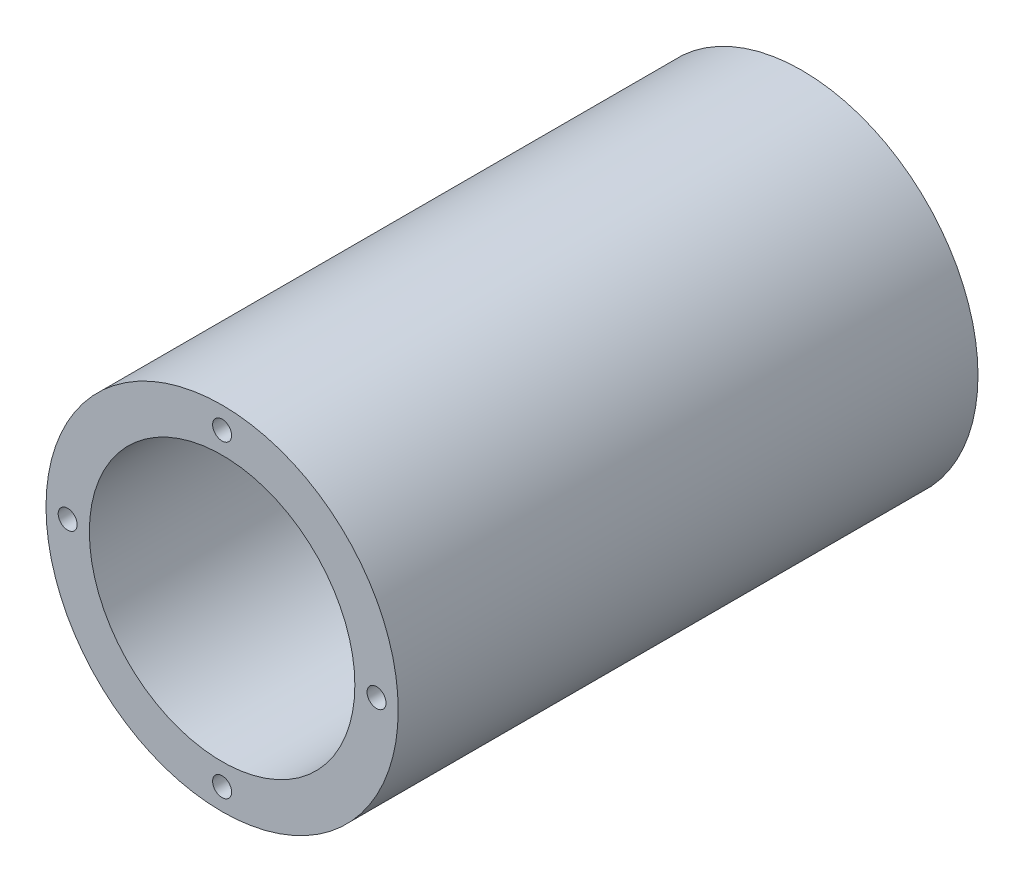
SolidWorks part; units mm, degrees
ref_plane "Alzado" through (0, 0, 0) normal (0, 0, 1) x (1, 0, 0)
ref_plane "Planta" through (0, 0, 0) normal (0, 1, 0) x (1, 0, 0)
ref_plane "Vista lateral" through (0, 0, 0) normal (1, 0, 0) x (0, 0, -1)
sketch "Croquis1" plane through (0, 0, 0) normal (0, 0, 1) x (1, 0, 0)
  circle A0 centre (0, 0) radius 32.5
  circle A1 centre (0, 0) radius 24.5
  dimension "D1" = 65
  dimension "D2" = 8
extrude "Boss-Extrude1" add sketch "Croquis1" along normal blind 107
sketch "Sketch1" plane through (0, 0, 0) normal (0, 0, -1) x (-1, 0, 0)
  line L0 (0, 0) -> (11.3818, 0) construction
  circle A0 centre (-28.5, 0) radius 1.5
  circle A1 centre (0, 28.5) radius 1.5
  circle A2 centre (28.5, 0) radius 1.5
  circle A3 centre (0, -28.5) radius 1.5
  circle A7 centre (0, 0) radius 28.5 construction
  circle A8 centre (0, 0) radius 24.5 construction
  point P2 (0, 0)
  point P8 (0, 0)
  point P9 (0, 0)
  point P17 (0, 0)
  dimension "D1" = 4
  dimension "D2" = 3
  dimension "D3" = 0
  dimension "D4" = 4
extrude "Cut-Extrude1" cut sketch "Sketch1" against normal blind 5
sketch "Sketch2" plane through (0, 0, 107) normal (0, 0, 1) x (1, 0, 0)
  circle A0 centre (-28.5, 0) radius 1.75
  circle A2 centre (0, 0) radius 28.5 construction
  circle A3 centre (0, 0) radius 24.5 construction
  circle A4 centre (0, 28.5) radius 1.75
  circle A5 centre (28.5, 0) radius 1.75
  circle A6 centre (0, -28.5) radius 1.75
  point P16 (0, 0)
  dimension "D1" = 4
  dimension "D2" = 3.5
  dimension "D3" = 4
extrude "Cut-Extrude2" cut sketch "Sketch2" against normal blind 5
